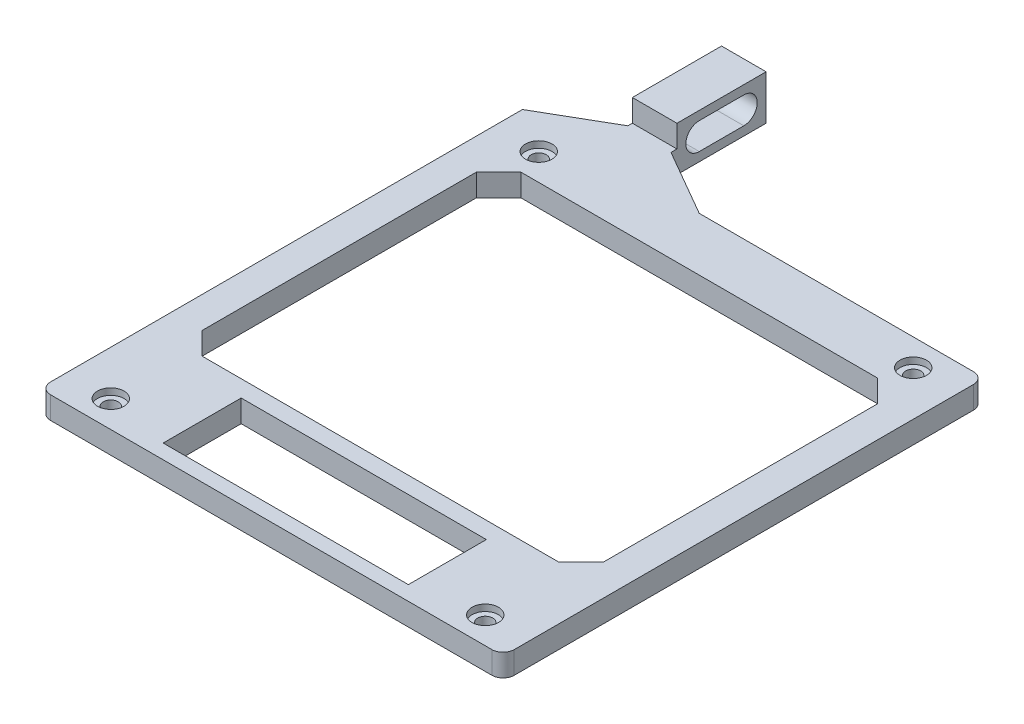
SolidWorks part; units mm, degrees
ref_plane "Front Plane" through (0, 0, 0) normal (0, 0, 1) x (1, 0, 0)
ref_plane "Top Plane" through (0, 0, 0) normal (0, 1, 0) x (1, 0, 0)
ref_plane "Right Plane" through (0, 0, 0) normal (1, 0, 0) x (0, 0, -1)
sketch "Sketch1" plane through (0, 0, 0) normal (0, 1, 0) x (1, 0, 0)
  line L1 (0, 0) -> (132.08, 0)
  line L2 (0, 0) -> (0, 137.16)
  line L3 (0, 137.16) -> (132.08, 137.16)
  line L4 (132.08, 0) -> (132.08, 137.16)
  dimension "D1" = 132.08
  dimension "D2" = 137.16
extrude "Boss-Extrude1" add sketch "Sketch1" along normal blind 6.35
ref_axis "Axis1" through (66.04, 6.35, 0) along (0, 0, -1)
ref_axis "Axis2" through (0, 6.35, -68.58) along (1, 0, 0)
hole_wizard "CBORE for #6 Button Head Cap Screw1" positions "Sketch4" profile "Sketch3" counterbore size "#6" standard "ANSI Inch" end condition up to next
sketch "Sketch4" plane through (0, 6.35, 0) normal (0, 1, 0) x (1, 0, 0)
  line L0 (12.7, 129.54) -> (119.38, 129.54)
  line L1 (119.38, 129.54) -> (119.38, 7.62)
  line L2 (119.38, 7.62) -> (12.7, 7.62)
  line L4 (12.7, 129.54) -> (12.7, 7.62)
  line L7 (66.04, 0) -> (66.04, 137.16) construction
  line L8 (0, 68.58) -> (132.08, 68.58) construction
  point P0 (12.7, 129.54)
  point P2 (119.38, 129.54)
  point P4 (119.38, 7.62)
  point P6 (12.7, 7.62)
  point P28 (66.04, 129.54)
  point P31 (119.38, 68.58)
  dimension "D1" = 106.68
  dimension "D2" = 121.92
sketch "Sketch3" plane through (12.7, 6.35, -129.54) normal (1, 0, 0) x (0, 0, 1)
  line L0 (0, 0) -> (0, 6.35)
  line L1 (0, 6.35) -> (2.1526, 6.35)
  line L3 (2.1526, 6.35) -> (2.1527, 1.8542)
  line L4 (2.1527, 1.8542) -> (3.7706, 1.8542)
  line L5 (3.7706, 1.8542) -> (3.7706, 0)
  line L7 (3.7706, 0) -> (0, 0)
  line L11 (0, -6.35) -> (0, 107.95) construction
  dimension "Thru Hole Dia." = 4.3053
  dimension "Thru Hole Depth" = 6.35
  dimension "C'Bore Dia." = 7.5413
  dimension "C'Bore Depth" = 1.8542
sketch "Sketch5" plane through (0, 6.35, 0) normal (0, 1, 0) x (1, 0, 0)
  line L0 (0, 68.58) -> (132.08, 68.58) construction
  line L1 (8.89, 15.24) -> (123.19, 15.24)
  line L2 (8.89, 15.24) -> (8.89, 121.92)
  line L3 (8.89, 121.92) -> (123.19, 121.92)
  line L4 (123.19, 15.24) -> (123.19, 121.92)
  line L5 (8.89, 15.24) -> (123.19, 121.92) construction
  line L6 (8.89, 121.92) -> (123.19, 15.24) construction
  line L7 (66.04, 0) -> (66.04, 137.16) construction
  point P0 (66.04, 68.58)
  dimension "D1" = 114.3
  dimension "D2" = 106.68
extrude "Cut-Extrude1" cut sketch "Sketch5" against normal through all
sketch "Sketch6" plane through (0, 0, 0) normal (0, -1, 0) x (-1, 0, 0)
  line L0 (-132.08, 137.16) -> (0, 137.16) construction
  line L1 (-19.05, 137.16) -> (-31.75, 137.16)
  line L2 (-19.05, 137.16) -> (-19.05, 175.26)
  line L3 (-19.05, 175.26) -> (-31.75, 175.26)
  line L4 (-31.75, 137.16) -> (-31.75, 175.26)
  point P5 (0, 0)
  dimension "D1" = 12.7
  dimension "D2" = 38.1
  dimension "D3" = 19.05
extrude "Boss-Extrude2" add sketch "Sketch6" against normal blind 6.35
sketch "Sketch7" plane through (0, 0, -175.26) normal (0, 0, -1) x (-1, 0, 0)
  line L3 (-19.05, 6.35) -> (-19.05, 0) construction
  line L4 (-19.05, 6.35) -> (-31.75, 6.35)
  line L5 (-19.05, 6.35) -> (-19.05, 12.7)
  line L6 (-19.05, 12.7) -> (-31.75, 12.7)
  line L7 (-31.75, 6.35) -> (-31.75, 12.7)
  point P0 (0, 6.35)
  dimension "D1" = 6.35
extrude "Boss-Extrude3" add sketch "Sketch7" against normal blind 25.4
sketch "Sketch8" plane through (19.05, 0, 0) normal (-1, 0, 0) x (0, 0, 1)
  line L0 (-175.26, 6.35) -> (-149.86, 6.35)
  line L1 (-175.26, 12.7) -> (-175.26, 0) construction
  line L2 (-149.86, 6.35) -> (-149.86, 12.7) construction
  line L3 (-168.91, 6.35) -> (-156.21, 6.35) construction
  line L4 (-168.91, 10.16) -> (-156.21, 10.16)
  line L5 (-168.91, 2.54) -> (-156.21, 2.54)
  arc A0 (-168.91, 10.16) -> (-168.91, 2.54) centre (-168.91, 6.35) ccw
  arc A1 (-156.21, 2.54) -> (-156.21, 10.16) centre (-156.21, 6.35) ccw
  point P4 (0, 0)
  point P8 (-162.56, 6.35)
  dimension "D1" = 3.81
  dimension "D2" = 6.35
extrude "Cut-Extrude2" cut sketch "Sketch8" against normal up to next contours L5 A1 L0 A0 | L0 A1 L4 A0 region at (19.05, 8.1628, -162.56) region at (19.05, 4.5372, -162.56)
ref_axis "Axis3" through (31.75, 6.35, -162.56) along (-1, 0, 0)
ref_axis "Axis4" through (31.75, 6.35, -156.21) along (-1, 0, 0)
sketch "Sketch9" plane through (0, 6.35, 0) normal (0, 1, 0) x (1, 0, 0)
  line L7 (66.04, 15.24) -> (66.04, 0) construction
  line L8 (8.89, 15.24) -> (123.19, 15.24) construction
  line L9 (0, 0) -> (132.08, 0) construction
  line L10 (100.965, 15.24) -> (31.115, 15.24)
  line L11 (31.115, 15.24) -> (31.115, 4.1275)
  line L12 (31.115, 4.1275) -> (100.965, 4.1275)
  line L13 (100.965, 15.24) -> (100.965, 4.1275)
  point P10 (66.04, 4.1275)
  dimension "D1" = 34.925
  dimension "D2" = 11.1125
extrude "Cut-Extrude3" cut sketch "Sketch9" against normal up to next
sketch "Sketch11" plane through (0, 6.35, 0) normal (0, 1, 0) x (1, 0, 0)
  line L3 (31.115, 4.1275) -> (100.965, 4.1275) construction
  line L4 (31.115, 15.24) -> (31.115, 4.1275) construction
  line L5 (8.89, 15.24) -> (31.115, 15.24)
  line L6 (100.965, 15.24) -> (123.19, 15.24)
  line L7 (100.965, 15.24) -> (100.965, 26.3525) construction
  line L8 (31.115, 4.1275) -> (100.965, 4.1275) construction
  line L9 (31.115, 26.3525) -> (31.115, 15.24) construction
  line L10 (31.115, 15.24) -> (100.965, 15.24) construction
  line L11 (31.115, 26.3525) -> (100.965, 26.3525)
  line L15 (8.89, 121.92) -> (8.89, 15.24) construction
  line L16 (123.19, 15.24) -> (123.19, 121.92) construction
  line L17 (8.89, 31.115) -> (123.19, 31.115)
  line L18 (31.115, 26.3525) -> (31.115, 15.24)
  line L19 (100.965, 15.24) -> (100.965, 26.3525)
  line L20 (123.19, 15.24) -> (123.19, 31.115)
  line L21 (8.89, 15.24) -> (8.89, 31.115)
  dimension "D1" = 4.7625
  dimension "D2" = 11.1125
extrude "Boss-Extrude4" add sketch "Sketch11" against normal up to surface (6.35 mm away) up to face at (66.04, 0, -39.1319)
chamfer "Chamfer1" distance 11.43 angle 60 1 edges at (19.05, 3.175, -137.16) first distance on face at (19.05, 6.35, -162.56)
fillet "Fillet1" radius 3.175 3 edges at (132.08, 3.175, -137.16) (132.08, 3.175, 0) (0, 3.175, 0)
chamfer "Chamfer2" distance 19.05 angle 30 1 edges at (31.75, 3.175, -137.16) first distance on face at (80.3275, 3.175, -137.16)
chamfer "Chamfer3" distance 6.35 angle 45 4 edges at (8.89, 3.175, -121.92) (123.19, 3.175, -31.115) (8.89, 3.175, -31.115) (123.19, 3.175, -121.92)
